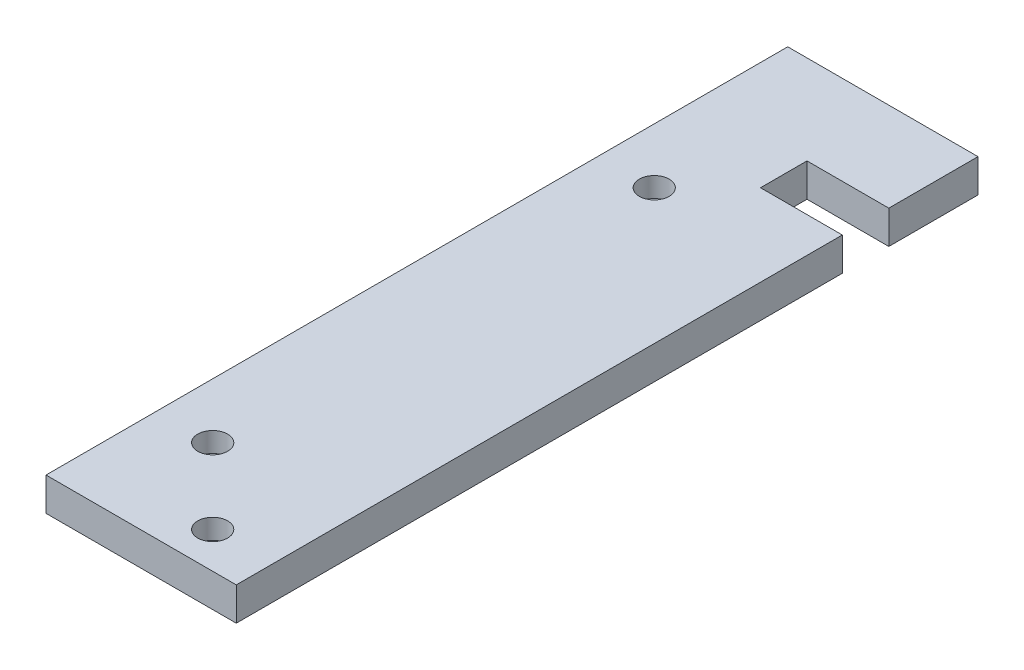
SolidWorks part; units mm, degrees
note: The reader was unsure of these and kept them because the rebuilt part matched: shared geometry of "草图1<12>", "草图1<13>".
ref_plane "前视基准面" through (0, 0, 0) normal (0, 0, 1) x (1, 0, 0)
ref_plane "上视基准面" through (0, 0, 0) normal (0, 1, 0) x (1, 0, 0)
ref_plane "右视基准面" through (0, 0, 0) normal (1, 0, 0) x (0, 0, -1)
other "Configuration Table"
sketch "草图1" plane through (0, 0, 0) normal (0, 1, 0) x (1, 0, 0)
  line L1 (0, 0) -> (-28.6421, 0)
  line L2 (0, 0) -> (0, 111.6592)
  line L3 (0, 111.6592) -> (-28.6421, 111.6592)
  line L4 (-28.6421, 0) -> (-28.6421, 111.6592)
  line L6 (0, 98.2317) -> (-12.3137, 98.2317)
  line L7 (0, 98.2317) -> (0, 91.2317)
  line L8 (0, 91.2317) -> (-12.3137, 91.2317)
  line L9 (-12.3137, 98.2317) -> (-12.3137, 91.2317)
  circle A2 centre (-20.3137, 83.2317) radius 1.5
  circle A4 centre (-20.3137, 16.7637) radius 1.5
  circle A5 centre (-9, 5.45) radius 1.5
  circle A6 centre (-20.3137, 83.2317) radius 2.25
  circle A8 centre (-9, 5.45) radius 2.25
  circle A9 centre (-20.3137, 16.7637) radius 2.25
  point P2 (0, 0)
  point P15 (-36.0524, 107.9623)
  dimension "D1" = 3
  dimension "D2" = 4.5
  dimension "D3" = 11.3137
  dimension "D4" = 11.3137
  dimension "D6" = 8
  dimension "D7" = 8
  dimension "D5" = 66.468
  dimension "D8" = 7
  dimension "D9" = 9
  dimension "D10" = 5.45
extrude "凸台-拉伸1" add sketch "草图1" along normal blind 5 contours L9 L6 L2 L3 L4 L1 L8 A9 A8 A6
extrude "切除-拉伸1" cut sketch "草图1<12>" along normal through all contours A4 | A5 | A2
sketch "草图1<12>" plane through (0, 0, 0) normal (0, 1, 0) x (1, 0, 0) same geometry as "草图1"
extrude "切除-拉伸3" cut sketch "草图1<13>" against normal offset from surface (3 mm away) 2 from surface at 5 contours A6 | A9 | A8 up to face at (-20.3137, 0, -81.7317) starting at face at (-20.3137, 5, -81.7317)
sketch "草图1<13>" plane through (0, 0, 0) normal (0, 1, 0) x (1, 0, 0) same geometry as "草图1"
